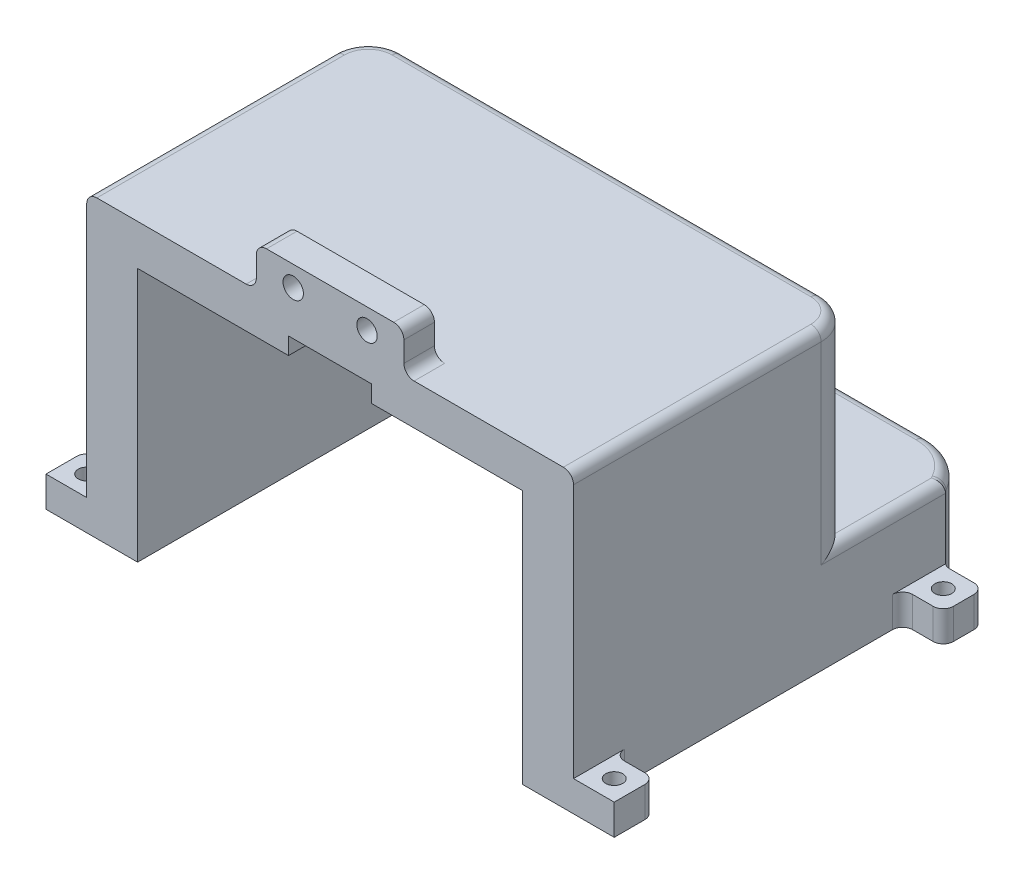
SolidWorks part; units mm, degrees
ref_plane "Front Plane" through (0, 0, 0) normal (0, 0, 1) x (1, 0, 0)
ref_plane "Top Plane" through (0, 0, 0) normal (0, 1, 0) x (1, 0, 0)
ref_plane "Right Plane" through (0, 0, 0) normal (1, 0, 0) x (0, 0, -1)
sketch "Sketch2" plane through (0, 0, 0) normal (0, 1, 0) x (1, 0, 0)
  line L0 (-83.989, 105.8585) -> (-83.989, 99.8585)
  line L1 (-80.989, 96.8585) -> (-74.989, 96.8585)
  line L2 (-71.989, 93.8585) -> (-71.989, 14.8585)
  line L3 (-74.989, 11.8585) -> (-80.989, 11.8585)
  line L4 (-83.989, 8.8585) -> (-83.989, -9.1415)
  line L5 (-80.989, -12.1415) -> (-74.989, -12.1415)
  line L6 (-71.989, -15.1415) -> (-71.989, -93.1415)
  line L7 (-74.989, -96.1415) -> (-80.989, -96.1415)
  line L8 (-83.989, -99.1415) -> (-83.989, -105.1415)
  line L9 (-80.989, -108.1415) -> (-74.1233, -108.1415)
  line L10 (-56.989, 108.8585) -> (56.511, 108.8585)
  line L11 (56.511, 108.8585) -> (56.511, 11.8585)
  line L12 (56.511, -78.1415) -> (58.261, -78.1415)
  line L13 (58.261, -78.1415) -> (58.261, -108.1415)
  line L14 (58.261, -108.1415) -> (26.0804, -108.1415)
  line L15 (-58.739, -18.2886) -> (-58.739, -108.1415)
  line L16 (24.761, -118.1415) -> (58.5216, -118.1415)
  line L17 (73.6452, -108.1415) -> (80.511, -108.1415)
  line L18 (83.511, -105.1415) -> (83.511, -99.1415)
  line L19 (80.511, -96.1415) -> (74.511, -96.1415)
  line L20 (71.511, -93.1415) -> (71.511, -15.1415)
  line L21 (74.511, -12.1415) -> (80.511, -12.1415)
  line L22 (83.511, -9.1415) -> (83.511, 8.8585)
  line L23 (80.511, 11.8585) -> (74.511, 11.8585)
  line L24 (71.511, 14.8585) -> (71.511, 93.8585)
  line L25 (74.511, 96.8585) -> (80.511, 96.8585)
  line L26 (83.511, 99.8585) -> (83.511, 105.8585)
  line L27 (80.511, 108.8585) -> (73.3929, 108.8585)
  line L28 (56.511, 118.8585) -> (-56.989, 118.8585)
  line L29 (-73.871, 108.8585) -> (-80.989, 108.8585)
  line L30 (-83.989, -0.1415) -> (83.511, -0.1415)
  line L31 (-56.989, 108.8585) -> (-56.989, 11.8585)
  line L32 (-56.989, 11.8585) -> (56.511, 11.8585)
  line L33 (-71.989, 93.8585) -> (-71.989, 109.5222)
  line L34 (71.511, 93.8585) -> (71.511, 109.5222)
  line L35 (71.511, 14.8585) -> (71.511, -0.1415)
  line L36 (-71.989, 14.8585) -> (-71.989, -0.1415)
  line L37 (-58.739, -108.1415) -> (26.0804, -108.1415)
  circle A0 centre (77.511, 5.8585) radius 2.5
  circle A1 centre (77.511, -6.1415) radius 2.5
  circle A2 centre (77.511, 102.8585) radius 2.5
  circle A3 centre (-77.43, 102.8585) radius 2.5
  circle A4 centre (-77.989, 5.8585) radius 2.5
  circle A5 centre (-77.989, -6.1415) radius 2.5
  circle A6 centre (-77.989, -102.1415) radius 2.5
  circle A7 centre (77.511, -102.1415) radius 2.5
  arc A8 (-83.989, 99.8585) -> (-80.989, 96.8585) centre (-80.989, 99.8585) ccw
  arc A9 (-71.989, 93.8585) -> (-74.989, 96.8585) centre (-74.989, 93.8585) ccw
  arc A10 (-74.989, 11.8585) -> (-71.989, 14.8585) centre (-74.989, 14.8585) ccw
  arc A11 (-80.989, 11.8585) -> (-83.989, 8.8585) centre (-80.989, 8.8585) ccw
  arc A12 (-83.989, -9.1415) -> (-80.989, -12.1415) centre (-80.989, -9.1415) ccw
  arc A13 (-71.989, -15.1415) -> (-74.989, -12.1415) centre (-74.989, -15.1415) ccw
  arc A14 (-74.989, -96.1415) -> (-71.989, -93.1415) centre (-74.989, -93.1415) ccw
  arc A15 (-80.989, -96.1415) -> (-83.989, -99.1415) centre (-80.989, -99.1415) ccw
  arc A16 (-83.989, -105.1415) -> (-80.989, -108.1415) centre (-80.989, -105.1415) ccw
  arc A17 (-71.3629, -109.9667) -> (-74.1233, -108.1415) centre (-74.1233, -111.1415) ccw
  arc A18 (58.5216, -118.1415) -> (70.8848, -109.9667) centre (58.5216, -104.7053) ccw
  arc A19 (73.6452, -108.1415) -> (70.8848, -109.9667) centre (73.6452, -111.1415) ccw
  arc A20 (80.511, -108.1415) -> (83.511, -105.1415) centre (80.511, -105.1415) ccw
  arc A21 (83.511, -99.1415) -> (80.511, -96.1415) centre (80.511, -99.1415) ccw
  arc A22 (71.511, -93.1415) -> (74.511, -96.1415) centre (74.511, -93.1415) ccw
  arc A23 (74.511, -12.1415) -> (71.511, -15.1415) centre (74.511, -15.1415) ccw
  arc A24 (80.511, -12.1415) -> (83.511, -9.1415) centre (80.511, -9.1415) ccw
  arc A25 (83.511, 8.8585) -> (80.511, 11.8585) centre (80.511, 8.8585) ccw
  arc A26 (71.511, 14.8585) -> (74.511, 11.8585) centre (74.511, 14.8585) ccw
  arc A27 (74.511, 96.8585) -> (71.511, 93.8585) centre (74.511, 93.8585) ccw
  arc A28 (80.511, 96.8585) -> (83.511, 99.8585) centre (80.511, 99.8585) ccw
  arc A29 (83.511, 105.8585) -> (80.511, 108.8585) centre (80.511, 105.8585) ccw
  arc A30 (70.762, 110.417) -> (73.3929, 108.8585) centre (73.3929, 111.8585) ccw
  arc A31 (70.762, 110.417) -> (56.511, 118.8585) centre (56.511, 102.6085) ccw
  arc A32 (-56.989, 118.8585) -> (-71.24, 110.417) centre (-56.989, 102.6085) ccw
  arc A33 (-73.871, 108.8585) -> (-71.24, 110.417) centre (-73.871, 111.8585) ccw
  arc A34 (-80.989, 108.8585) -> (-83.989, 105.8585) centre (-80.989, 105.8585) ccw
  dimension "D1" = 5
  dimension "D2" = 5
  dimension "D3" = 5
  dimension "D4" = 5
  dimension "D5" = 5
  dimension "D6" = 5
  dimension "D7" = 5
  dimension "D8" = 5
  dimension "D9" = 6
  dimension "D10" = 6
  dimension "D11" = 6
  dimension "D12" = 6
  dimension "D13" = 6
  dimension "D14" = 6
  dimension "D15" = 6
  dimension "D16" = 6
  dimension "D17" = 6
  dimension "D18" = 6
  dimension "D19" = 6
  dimension "D20" = 6
  dimension "D21" = 6
  dimension "D22" = 6
  dimension "D23" = 6
  dimension "D24" = 13.25
  dimension "D25" = 13.25
extrude "Boss-Extrude2" add sketch "Sketch2" along normal blind 87 contours A33 L33 L2 L36 L30 L35 L24 L34 A30 A31 L28 A32 L32 L31 L10 L11 | L10 L11 L32 L31 region at (-70.1411, 0, -108.7362)
sketch "Sketch3" plane through (0, 0, 0) normal (0, -1, 0) x (1, 0, 0)
  line L0 (56.511, -108.8585) -> (56.511, -11.8585) construction
  line L1 (-56.989, -108.8585) -> (56.511, -108.8585) construction
  line L2 (-56.989, -108.8585) -> (-56.989, -11.8585) construction
  line L4 (56.511, -108.8585) -> (56.511, -11.8585)
  line L5 (-56.989, -108.8585) -> (56.511, -108.8585)
  line L6 (-56.989, -108.8585) -> (-56.989, -11.8585)
  line L8 (-56.989, -11.8585) -> (-56.989, 0.1415)
  line L9 (-83.989, 0.1415) -> (83.511, 0.1415) construction
  line L10 (56.511, -11.8585) -> (56.511, 0.1415)
  line L11 (-56.989, 0.1415) -> (56.511, 0.1415)
extrude "Cut-Extrude2" cut sketch "Sketch3" against normal blind 15
sketch "Sketch4" plane through (0, 0, 0) normal (0, -1, 0) x (1, 0, 0)
  line L0 (-71.989, -93.8585) -> (-71.989, -109.5222) construction
  line L1 (-80.989, -96.8585) -> (-74.989, -96.8585) construction
  line L2 (-83.989, -105.8585) -> (-83.989, -99.8585) construction
  line L3 (-73.871, -108.8585) -> (-80.989, -108.8585) construction
  line L4 (83.511, -99.8585) -> (83.511, -105.8585) construction
  line L5 (80.511, -108.8585) -> (73.3929, -108.8585) construction
  line L6 (71.511, -93.8585) -> (71.511, -109.5222) construction
  line L7 (74.511, -96.8585) -> (80.511, -96.8585) construction
  line L8 (-83.989, -8.8585) -> (-83.989, 9.1415) construction
  line L9 (-71.989, -14.8585) -> (-71.989, 0.1415) construction
  line L10 (-74.989, -11.8585) -> (-80.989, -11.8585) construction
  line L11 (-83.989, 0.1415) -> (83.511, 0.1415) construction
  line L12 (83.511, 9.1415) -> (83.511, -8.8585) construction
  line L13 (80.511, -11.8585) -> (74.511, -11.8585) construction
  line L14 (71.511, -14.8585) -> (71.511, 0.1415) construction
  line L15 (-71.989, -93.8585) -> (-71.989, -109.5222)
  line L16 (-80.989, -96.8585) -> (-74.989, -96.8585)
  line L17 (-83.989, -105.8585) -> (-83.989, -99.8585)
  line L18 (-73.871, -108.8585) -> (-80.989, -108.8585)
  line L19 (83.511, -99.8585) -> (83.511, -105.8585)
  line L20 (80.511, -108.8585) -> (73.3929, -108.8585)
  line L21 (71.511, -93.8585) -> (71.511, -109.5222)
  line L22 (74.511, -96.8585) -> (80.511, -96.8585)
  line L23 (-83.989, -8.8585) -> (-83.989, 9.1415)
  line L24 (-71.989, -14.8585) -> (-71.989, 0.1415)
  line L25 (-74.989, -11.8585) -> (-80.989, -11.8585)
  line L26 (-83.989, 0.1415) -> (83.511, 0.1415)
  line L27 (83.511, 9.1415) -> (83.511, -8.8585)
  line L28 (80.511, -11.8585) -> (74.511, -11.8585)
  line L29 (71.511, -14.8585) -> (71.511, 0.1415)
  circle A0 centre (-77.43, -102.8585) radius 2.5 construction
  arc A1 (-74.989, -96.8585) -> (-71.989, -93.8585) centre (-74.989, -93.8585) ccw construction
  arc A2 (-80.989, -96.8585) -> (-83.989, -99.8585) centre (-80.989, -99.8585) ccw construction
  arc A3 (-83.989, -105.8585) -> (-80.989, -108.8585) centre (-80.989, -105.8585) ccw construction
  arc A4 (-71.24, -110.417) -> (-73.871, -108.8585) centre (-73.871, -111.8585) ccw construction
  circle A5 centre (77.511, -102.8585) radius 2.5 construction
  arc A6 (83.511, -99.8585) -> (80.511, -96.8585) centre (80.511, -99.8585) ccw construction
  arc A7 (80.511, -108.8585) -> (83.511, -105.8585) centre (80.511, -105.8585) ccw construction
  arc A8 (73.3929, -108.8585) -> (70.762, -110.417) centre (73.3929, -111.8585) ccw construction
  arc A9 (71.511, -93.8585) -> (74.511, -96.8585) centre (74.511, -93.8585) ccw construction
  circle A10 centre (77.511, -5.8585) radius 2.5 construction
  circle A11 centre (-77.989, -5.8585) radius 2.5 construction
  arc A12 (-83.989, -8.8585) -> (-80.989, -11.8585) centre (-80.989, -8.8585) ccw construction
  arc A13 (-71.989, -14.8585) -> (-74.989, -11.8585) centre (-74.989, -14.8585) ccw construction
  arc A14 (80.511, -11.8585) -> (83.511, -8.8585) centre (80.511, -8.8585) ccw construction
  arc A15 (74.511, -11.8585) -> (71.511, -14.8585) centre (74.511, -14.8585) ccw construction
  circle A16 centre (-77.43, -102.8585) radius 2.5
  arc A17 (-74.989, -96.8585) -> (-71.989, -93.8585) centre (-74.989, -93.8585) ccw
  arc A18 (-80.989, -96.8585) -> (-83.989, -99.8585) centre (-80.989, -99.8585) ccw
  arc A19 (-83.989, -105.8585) -> (-80.989, -108.8585) centre (-80.989, -105.8585) ccw
  arc A20 (-71.24, -110.417) -> (-73.871, -108.8585) centre (-73.871, -111.8585) ccw
  circle A21 centre (77.511, -102.8585) radius 2.5
  arc A22 (83.511, -99.8585) -> (80.511, -96.8585) centre (80.511, -99.8585) ccw
  arc A23 (80.511, -108.8585) -> (83.511, -105.8585) centre (80.511, -105.8585) ccw
  arc A24 (73.3929, -108.8585) -> (70.762, -110.417) centre (73.3929, -111.8585) ccw
  arc A25 (71.511, -93.8585) -> (74.511, -96.8585) centre (74.511, -93.8585) ccw
  circle A26 centre (77.511, -5.8585) radius 2.5
  circle A27 centre (-77.989, -5.8585) radius 2.5
  arc A28 (-83.989, -8.8585) -> (-80.989, -11.8585) centre (-80.989, -8.8585) ccw
  arc A29 (-71.989, -14.8585) -> (-74.989, -11.8585) centre (-74.989, -14.8585) ccw
  arc A30 (80.511, -11.8585) -> (83.511, -8.8585) centre (80.511, -8.8585) ccw
  arc A31 (74.511, -11.8585) -> (71.511, -14.8585) centre (74.511, -14.8585) ccw
  line M4 (-71.989, 0.1415) -> (-71.989, -109.5222)
  line M10 (71.511, -109.5222) -> (71.511, 0.1415)
extrude "Boss-Extrude3" add sketch "Sketch4" against normal blind 9 contours A20 A17 L16 A18 L17 A19 L18 A16 M4 | A29 L26 L23 A28 L25 A27 M4 | A25 A24 L20 A23 L19 A22 L22 A21 M10 | A31 L28 A30 L27 L26 A26 M10 region at (-72.1864, 0, -101.6904) region at (72.2501, 0, -96.1194) region at (77.511, 0, -0.0506) region at (-72.7319, 0, -12.6014)
sketch "Sketch5" plane through (0, 87, 0) normal (0, 1, 0) x (1, 0, 0)
  line L0 (-71.989, 82.8585) -> (71.511, 82.8585)
  line L4 (-71.989, 109.5222) -> (-71.989, -0.1415)
  line L5 (-71.989, -0.1415) -> (71.511, -0.1415)
  line L6 (71.511, -0.1415) -> (71.511, 109.5222)
  line L7 (56.511, 118.8585) -> (-56.989, 118.8585)
  line L8 (-71.989, 109.5222) -> (-71.989, -0.1415)
  line L9 (-71.989, -0.1415) -> (71.511, -0.1415)
  line L10 (71.511, -0.1415) -> (71.511, 109.5222)
  line L11 (56.511, 118.8585) -> (-56.989, 118.8585)
  arc A4 (-71.989, 109.5222) -> (-71.24, 110.417) centre (-73.871, 111.8585) ccw
  arc A5 (70.762, 110.417) -> (71.511, 109.5222) centre (73.3929, 111.8585) ccw
  arc A6 (70.762, 110.417) -> (56.511, 118.8585) centre (56.511, 102.6085) ccw
  arc A7 (-56.989, 118.8585) -> (-71.24, 110.417) centre (-56.989, 102.6085) ccw
  arc A8 (-71.989, 109.5222) -> (-71.24, 110.417) centre (-73.871, 111.8585) ccw
  arc A9 (70.762, 110.417) -> (71.511, 109.5222) centre (73.3929, 111.8585) ccw
  arc A10 (70.762, 110.417) -> (56.511, 118.8585) centre (56.511, 102.6085) ccw
  arc A11 (-56.989, 118.8585) -> (-71.24, 110.417) centre (-56.989, 102.6085) ccw
  arc M10 (-71.24, 110.417) -> (-71.989, 109.5222) centre (-73.871, 111.8585) cw
  line M11 (-71.989, 109.5222) -> (-71.989, -0.1415)
  line M13 (71.511, -0.1415) -> (71.511, 109.5222)
  arc M14 (71.511, 109.5222) -> (70.762, 110.417) centre (73.3929, 111.8585) cw
  arc M15 (70.762, 110.417) -> (56.511, 118.8585) centre (56.511, 102.6085) ccw
  line M16 (56.511, 118.8585) -> (-56.989, 118.8585)
  arc M17 (-56.989, 118.8585) -> (-71.24, 110.417) centre (-56.989, 102.6085) ccw
  dimension "D2" = 36
  dimension "D1" = 0
extrude "Cut-Extrude3" cut sketch "Sketch5" against normal blind 57 contours L0 M11 M13 M14 M15 M16 M17 M10 region at (-0.239, 87, -100.6092)
sketch "Sketch6" plane through (0, 15, 0) normal (0, -1, 0) x (1, 0, 0)
  line L0 (-56.989, -67.8585) -> (56.511, -67.8585)
  line L4 (-56.989, -108.8585) -> (56.511, -108.8585)
  line L5 (56.511, -108.8585) -> (56.511, 0.1415)
  line L6 (56.511, 0.1415) -> (-56.989, 0.1415)
  line L7 (-56.989, 0.1415) -> (-56.989, -108.8585)
  line L8 (-56.989, -108.8585) -> (56.511, -108.8585)
  line L9 (56.511, -108.8585) -> (56.511, 0.1415)
  line L10 (56.511, 0.1415) -> (-56.989, 0.1415)
  line L11 (-56.989, 0.1415) -> (-56.989, -108.8585)
  line M7 (56.511, -108.8585) -> (56.511, 0.1415)
  line M8 (56.511, 0.1415) -> (-56.989, 0.1415)
  line M9 (-56.989, 0.1415) -> (-56.989, -108.8585)
  dimension "D2" = 68
  dimension "D1" = 0
extrude "Cut-Extrude4" cut sketch "Sketch6" against normal blind 60 contours L0 M9 M7 M8 region at (-0.239, 15, -33.8585)
sketch "Sketch7" plane through (0, 0, -82.8585) normal (0, 0, -1) x (-1, 0, 0)
  line L0 (71.989, 30) -> (-71.511, 87) construction
  line L1 (-71.511, 30) -> (71.989, 87) construction
  circle A0 centre (-8.2432, 66.9434) radius 1.5
  circle A1 centre (-8.4232, 50.1034) radius 1.5
  circle A2 centre (8.4968, 50.1034) radius 1.5
  circle A3 centre (8.6768, 66.9434) radius 1.5
  circle A4 centre (-10.2044, 38.5328) radius 1.5
  circle A5 centre (10.6356, 38.5328) radius 1.5
  circle A6 centre (10.6356, 78.4228) radius 1.5
  circle A7 centre (-10.2044, 78.4228) radius 1.5
  circle A8 centre (0.239, 58.5) radius 6
  point P8 (0.239, 58.5)
  point P9 (-67.2705, 108.0639)
  dimension "D1" = 3
  dimension "D2" = 3
  dimension "D3" = 3
  dimension "D4" = 3
  dimension "D5" = 3
  dimension "D6" = 3
  dimension "D7" = 3
  dimension "D8" = 3
  dimension "D9" = 16.92
  dimension "D10" = 16.92
  dimension "D11" = 39.89
  dimension "D12" = 39.89
  dimension "D13" = 20.84
  dimension "D14" = 20.84
  dimension "D15" = 16.84
  dimension "D16" = 16.84
extrude "Cut-Extrude5" cut sketch "Sketch7" against normal blind 60
sketch "Sketch8" plane through (0, 0, 0.1415) normal (0, 0, 1) x (1, 0, 0)
  line L0 (12.011, 75) -> (12.011, 80)
  line L1 (12.011, 80) -> (-12.489, 80)
  line L2 (-12.489, 80) -> (-12.489, 75)
  line L3 (-12.489, 75) -> (12.011, 75)
  line L12 (-56.989, 0) -> (-56.989, 75)
  line L13 (-56.989, 75) -> (56.511, 75)
  line L14 (56.511, 75) -> (56.511, 0)
  line L15 (56.511, 0) -> (83.511, 0)
  line L16 (83.511, 0) -> (83.511, 9)
  line L17 (83.511, 9) -> (71.511, 9)
  line L18 (71.511, 9) -> (71.511, 87)
  line L19 (71.511, 87) -> (-71.989, 87)
  line L20 (-71.989, 87) -> (-71.989, 9)
  line L21 (-71.989, 9) -> (-83.989, 9)
  line L22 (-83.989, 9) -> (-83.989, 0)
  line L23 (-83.989, 0) -> (-56.989, 0)
  line L24 (-56.989, 0) -> (-56.989, 75)
  line L25 (-56.989, 75) -> (56.511, 75)
  line L26 (56.511, 75) -> (56.511, 0)
  line L27 (56.511, 0) -> (83.511, 0)
  line L28 (83.511, 0) -> (83.511, 9)
  line L29 (83.511, 9) -> (71.511, 9)
  line L30 (71.511, 9) -> (71.511, 87)
  line L31 (71.511, 87) -> (-71.989, 87)
  line L32 (-71.989, 87) -> (-71.989, 9)
  line L33 (-71.989, 9) -> (-83.989, 9)
  line L34 (-83.989, 9) -> (-83.989, 0)
  line L35 (-83.989, 0) -> (-56.989, 0)
  line M18 (-56.989, 75) -> (56.511, 75)
  dimension "D2" = 44.5
  dimension "D3" = 44.5
  dimension "D4" = 5
  dimension "D1" = 0
extrude "Cut-Extrude6" cut sketch "Sketch8" against normal blind 68 contours L1 L2 L0 M18 region at (-0.239, 77.5, 0.1415)
sketch "Sketch9" plane through (0, 0, 0.1415) normal (0, 0, 1) x (1, 0, 0)
  line L0 (-21.989, 87) -> (-21.989, 99)
  line L1 (-71.989, 87) -> (71.511, 87) construction
  line L2 (-21.989, 99) -> (21.511, 99)
  line L3 (21.511, 99) -> (21.511, 87)
  line L4 (-21.989, 87) -> (21.511, 87)
  line L5 (-71.989, 87) -> (-71.989, 9) construction
  line L6 (71.511, 87) -> (71.511, 9) construction
  line L7 (-0.239, 99) -> (-0.239, 87)
  line L8 (-21.989, 99) -> (-0.239, 87) construction
  line L9 (-0.239, 87) -> (21.511, 99) construction
  line L10 (21.511, 87) -> (-0.239, 99) construction
  line L11 (-0.239, 99) -> (-21.989, 87) construction
  circle A0 centre (-11.114, 93) radius 3
  circle A1 centre (10.636, 93) radius 3
  line M13 (71.511, 87) -> (-71.989, 87)
  dimension "D4" = 6
  dimension "D5" = 6
  dimension "D1" = 50
  dimension "D2" = 50
  dimension "D3" = 12
extrude "Boss-Extrude4" add sketch "Sketch9" against normal blind 9 contours L7 L2 L0 L4 A0 | L2 L7 L3 A1 M13 region at (-21.7406, 93, 0.1415) region at (0.0094, 93, 0.1415)
fillet "Fillet1" radius 3 10 edges at (71.0925, 30, -109.9328) (-71.5706, 30, -109.9328) (-65.2708, 30, -116.5898) (-71.989, 30, -96.1904) (-0.239, 30, -118.8585) (64.7927, 30, -116.5898) (71.511, 30, -96.1904) (-71.989, 87, -41.3585) (-0.239, 87, -82.8585) (71.511, 87, -41.3585)
fillet "Fillet2" radius 10 4 edges at (70.6323, 86.1213, -81.9799) (-71.1104, 86.1213, -81.9799) (-71.989, 55.5, -82.8585) (71.511, 55.5, -82.8585)
fillet "Fillet3" radius 3 4 edges at (21.511, 87, -4.3585) (21.511, 99, -4.3585) (-21.989, 99, -4.3585) (-21.989, 87, -4.3585)
sketch "Sketch10" plane through (0, 0, 0.1415) normal (0, 0, 1) x (1, 0, 0)
  line L0 (-68.989, 87) -> (-24.989, 87) construction
  line L1 (-68.989, 87) -> (-24.989, 87)
  line L2 (-24.989, 87) -> (24.511, 87) construction
  line L22 (21.511, 90) -> (21.511, 96)
  line L23 (18.511, 99) -> (-18.989, 99)
  line L24 (-21.989, 96) -> (-21.989, 90)
  line L25 (-24.989, 87) -> (-68.989, 87)
  line L26 (-71.989, 84) -> (-71.989, 9)
  line L27 (-71.989, 9) -> (-83.989, 9)
  line L28 (-83.989, 9) -> (-83.989, 0)
  line L29 (-83.989, 0) -> (-56.989, 0)
  line L30 (-56.989, 0) -> (-56.989, 75)
  line L31 (-56.989, 75) -> (-12.489, 75)
  line L32 (-12.489, 75) -> (-12.489, 80)
  line L33 (-12.489, 80) -> (12.011, 80)
  line L34 (12.011, 80) -> (12.011, 75)
  line L35 (12.011, 75) -> (56.511, 75)
  line L36 (56.511, 75) -> (56.511, 0)
  line L37 (56.511, 0) -> (83.511, 0)
  line L38 (83.511, 0) -> (83.511, 9)
  line L39 (83.511, 9) -> (71.511, 9)
  line L40 (71.511, 9) -> (71.511, 84)
  line L41 (68.511, 87) -> (24.511, 87)
  line L42 (21.511, 90) -> (21.511, 96)
  line L43 (18.511, 99) -> (-18.989, 99)
  line L44 (-21.989, 96) -> (-21.989, 90)
  line L45 (-24.989, 87) -> (-68.989, 87)
  line L46 (-71.989, 84) -> (-71.989, 9)
  line L47 (-71.989, 9) -> (-83.989, 9)
  line L48 (-83.989, 9) -> (-83.989, 0)
  line L49 (-83.989, 0) -> (-56.989, 0)
  line L50 (-56.989, 0) -> (-56.989, 75)
  line L51 (-56.989, 75) -> (-12.489, 75)
  line L52 (-12.489, 75) -> (-12.489, 80)
  line L53 (-12.489, 80) -> (12.011, 80)
  line L54 (12.011, 80) -> (12.011, 75)
  line L55 (12.011, 75) -> (56.511, 75)
  line L56 (56.511, 75) -> (56.511, 0)
  line L57 (56.511, 0) -> (83.511, 0)
  line L58 (83.511, 0) -> (83.511, 9)
  line L59 (83.511, 9) -> (71.511, 9)
  line L60 (71.511, 9) -> (71.511, 84)
  line L61 (68.511, 87) -> (24.511, 87)
  arc A6 (21.511, 96) -> (18.511, 99) centre (18.511, 96) ccw
  arc A7 (-18.989, 99) -> (-21.989, 96) centre (-18.989, 96) ccw
  arc A8 (-24.989, 87) -> (-21.989, 90) centre (-24.989, 90) ccw
  arc A9 (-68.989, 87) -> (-71.989, 84) centre (-68.989, 84) ccw
  arc A10 (71.511, 84) -> (68.511, 87) centre (68.511, 84) ccw
  arc A11 (21.511, 90) -> (24.511, 87) centre (24.511, 90) ccw
  arc A12 (21.511, 96) -> (18.511, 99) centre (18.511, 96) ccw
  arc A13 (-18.989, 99) -> (-21.989, 96) centre (-18.989, 96) ccw
  arc A14 (-24.989, 87) -> (-21.989, 90) centre (-24.989, 90) ccw
  arc A15 (-68.989, 87) -> (-71.989, 84) centre (-68.989, 84) ccw
  arc A16 (71.511, 84) -> (68.511, 87) centre (68.511, 84) ccw
  arc A17 (21.511, 90) -> (24.511, 87) centre (24.511, 90) ccw
  dimension "D1" = 0
